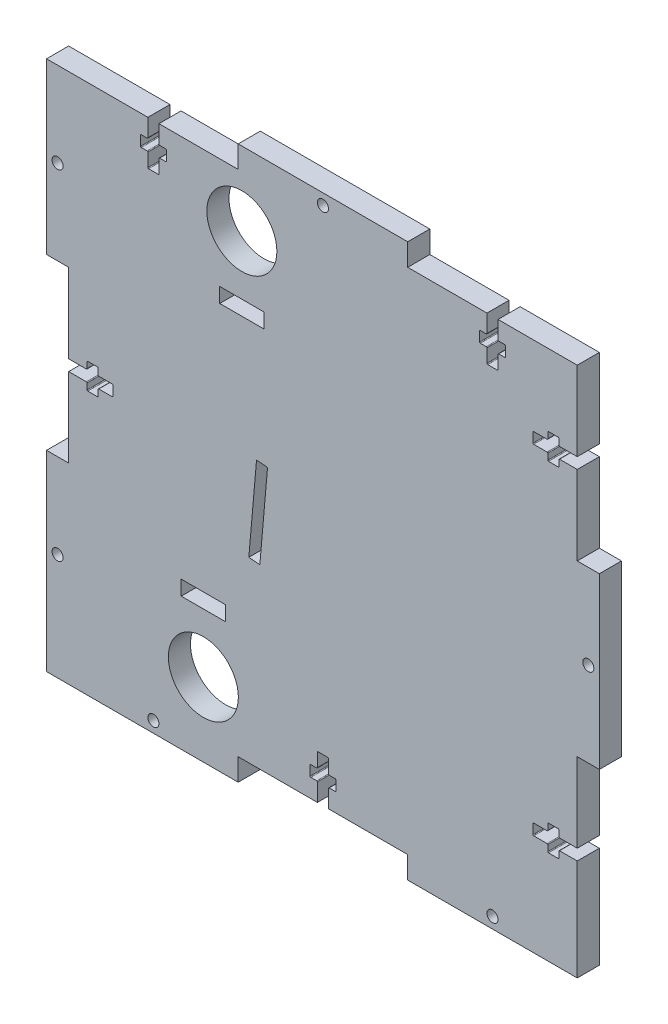
SolidWorks part; units mm, degrees
ref_plane "Front Plane" through (0, 0, 0) normal (0, 0, 1) x (1, 0, 0)
ref_plane "Top Plane" through (0, 0, 0) normal (0, 1, 0) x (1, 0, 0)
ref_plane "Right Plane" through (0, 0, 0) normal (1, 0, 0) x (0, 0, -1)
sketch "Sketch1" plane through (0, 0, 0) normal (0, 0, 1) x (1, 0, 0)
  line L0 (-69, 69) -> (-23, 69)
  line L5 (-75, -75) -> (75, -75) construction
  line L6 (-75, -75) -> (-75, 75) construction
  line L7 (-75, 75) -> (75, 75) construction
  line L8 (75, -75) -> (75, 75) construction
  line L9 (75, 23) -> (69, 23)
  line L10 (69, -23) -> (75, -23)
  line L11 (-69, -69) -> (69, -69) construction
  line L12 (-69, -69) -> (-69, 69) construction
  line L13 (-69, 69) -> (69, 69) construction
  line L14 (69, -69) -> (69, 69) construction
  line L15 (-69, -69) -> (69, 69) construction
  line L16 (69, -69) -> (69, -23)
  line L17 (-23, 69) -> (-23, 75)
  line L18 (-23, 75) -> (23, 75)
  line L19 (23, 75) -> (23, 69)
  line L20 (23, 69) -> (69, 69)
  line L21 (75, -23) -> (75, 23)
  line L22 (69, 23) -> (69, 69)
  line L23 (-75, 23) -> (-69, 23)
  line L24 (-69, 69) -> (-75, 69)
  line L25 (-75, 69) -> (-75, 23)
  line L26 (69, -69) -> (69, -75)
  line L27 (69, -75) -> (23, -75)
  line L28 (23, -75) -> (23, -69)
  line L29 (23, -69) -> (-23, -69)
  line L30 (-23, -69) -> (-23, -75)
  line L31 (-23, -75) -> (-69, -75)
  line L32 (-69, -75) -> (-69, -69) construction
  line L33 (-69, 23) -> (-69, -23)
  line L34 (-69, -23) -> (-75, -23)
  line L35 (-75, -23) -> (-75, -69)
  line L36 (-75, -69) -> (-69, -69) construction
  line L37 (-46, 69) -> (-46, -75) construction
  line L38 (-69, 69) -> (69, -69) construction
  line L39 (-75, -75) -> (-69, -75)
  line L40 (-75, -75) -> (-75, -69)
  point P0 (0, 0)
  point P6 (-7, -7)
  point P26 (0, -75)
  point P27 (-75, 0)
  dimension "D1" = 150
  dimension "D2" = 150
  dimension "D5" = 46
  dimension "D3" = 6
  dimension "D6" = 6
  dimension "D7" = 6
extrude "Box Side" add sketch "Sketch1" along normal blind 6
sketch "Sketch2" plane through (0, 0, 6) normal (0, 0, 1) x (1, 0, 0)
  line L0 (23, 72) -> (-23, 72) construction
  line L1 (23, 75) -> (23, 69) construction
  line L2 (-23, 69) -> (-23, 75) construction
  line L3 (-46, 69) -> (-46, -75) construction
  line L5 (0, 75) -> (0, 69) construction
  line L6 (-23, 75) -> (23, 75) construction
  line L7 (-69, 69) -> (69, 69) construction
  line L16 (-46, 69) -> (-46, -75) construction
  line L21 (0, -69) -> (0, 69) construction
  line L35 (-69, 69) -> (-23, 69) construction
  line L36 (-44.5, 69) -> (-44.5, 64.2)
  line L37 (-44.3, 64) -> (-42.7, 64)
  line L38 (-42.5, 63.8) -> (-42.5, 61.2)
  line L39 (-42.7, 61) -> (-44.3, 61)
  line L40 (-44.5, 60.8) -> (-44.5, 57.2)
  line L46 (-44.7, 57) -> (-47.3, 57)
  line L48 (-44.5, 69) -> (-47.5, 69)
  line L51 (-47.5, 60.8) -> (-47.5, 57.2)
  line L52 (-49.3, 61) -> (-47.7, 61)
  line L53 (-49.5, 63.8) -> (-49.5, 61.2)
  line L54 (-47.7, 64) -> (-49.3, 64)
  line L55 (-47.5, 69) -> (-47.5, 64.2)
  line L56 (47.5, 69) -> (47.5, 64.2)
  line L57 (47.7, 64) -> (49.3, 64)
  line L58 (49.5, 63.8) -> (49.5, 61.2)
  line L59 (49.3, 61) -> (47.7, 61)
  line L60 (47.5, 60.8) -> (47.5, 57.2)
  line L61 (44.5, 69) -> (47.5, 69)
  line L62 (44.7, 57) -> (47.3, 57)
  line L63 (44.5, 60.8) -> (44.5, 57.2)
  line L64 (42.7, 61) -> (44.3, 61)
  line L65 (42.5, 63.8) -> (42.5, 61.2)
  line L66 (44.3, 64) -> (42.7, 64)
  line L67 (44.5, 69) -> (44.5, 64.2)
  line L68 (-69, -69) -> (69, 69) construction
  line L69 (-69, -69) -> (69, 69) construction
  line L70 (75, 0) -> (69, 0) construction
  line L71 (72, 23) -> (72, -23) construction
  line L72 (69, 44.5) -> (64.2, 44.5)
  line L73 (64, 44.3) -> (64, 42.7)
  line L74 (63.8, 42.5) -> (61.2, 42.5)
  line L75 (61, 42.7) -> (61, 44.3)
  line L76 (60.8, 44.5) -> (57.2, 44.5)
  line L77 (57, 44.7) -> (57, 47.3)
  line L78 (69, 44.5) -> (69, 47.5)
  line L79 (60.8, 47.5) -> (57.2, 47.5)
  line L80 (61, 49.3) -> (61, 47.7)
  line L81 (63.8, 49.5) -> (61.2, 49.5)
  line L82 (64, 47.7) -> (64, 49.3)
  line L83 (69, 47.5) -> (64.2, 47.5)
  line L84 (69, -47.5) -> (64.2, -47.5)
  line L85 (64, -47.7) -> (64, -49.3)
  line L86 (63.8, -49.5) -> (61.2, -49.5)
  line L87 (61, -49.3) -> (61, -47.7)
  line L88 (60.8, -47.5) -> (57.2, -47.5)
  line L89 (69, -44.5) -> (69, -47.5)
  line L90 (57, -44.7) -> (57, -47.3)
  line L91 (60.8, -44.5) -> (57.2, -44.5)
  line L92 (61, -42.7) -> (61, -44.3)
  line L93 (63.8, -42.5) -> (61.2, -42.5)
  line L94 (64, -44.3) -> (64, -42.7)
  line L95 (69, -44.5) -> (64.2, -44.5)
  line L120 (-69, 69) -> (69, -69) construction
  line L121 (-69, 69) -> (69, -69) construction
  line L122 (-1.5, -69) -> (1.5, -69)
  line L123 (-23, -69) -> (23, -69) construction
  line L124 (1.5, -69) -> (1.5, -64.2)
  line L125 (1.7, -64) -> (3.3, -64)
  line L126 (3.5, -63.8) -> (3.5, -61.2)
  line L127 (3.3, -61) -> (1.7, -61)
  line L128 (1.5, -60.8) -> (1.5, -57.2)
  line L129 (1.3, -57) -> (-1.3, -57)
  line L130 (-1.5, -60.8) -> (-1.5, -57.2)
  line L131 (-3.3, -61) -> (-1.7, -61)
  line L132 (-3.5, -63.8) -> (-3.5, -61.2)
  line L133 (-1.7, -64) -> (-3.3, -64)
  line L134 (-1.5, -69) -> (-1.5, -64.2)
  line L135 (-69, -1.5) -> (-64.2, -1.5)
  line L136 (-64, -1.7) -> (-64, -3.3)
  line L137 (-63.8, -3.5) -> (-61.2, -3.5)
  line L138 (-61, -3.3) -> (-61, -1.7)
  line L139 (-60.8, -1.5) -> (-57.2, -1.5)
  line L140 (-57, 1.3) -> (-57, -1.3)
  line L141 (-60.8, 1.5) -> (-57.2, 1.5)
  line L142 (-61, 3.3) -> (-61, 1.7)
  line L143 (-63.8, 3.5) -> (-61.2, 3.5)
  line L144 (-64, 1.7) -> (-64, 3.3)
  line L145 (-69, 1.5) -> (-64.2, 1.5)
  line L146 (-69, -1.5) -> (-69, 1.5)
  line L147 (-69, -72) -> (-23, -72) construction
  line L148 (-23, 69) -> (-75, 69) construction
  line L149 (-23, -75) -> (-23, -69) construction
  line L150 (-69, -69) -> (-69, -75) construction
  line L151 (-75, -75) -> (-23, -75) construction
  circle A0 centre (0, 72) radius 1.5
  arc A1 (-44.5, 57.2) -> (-44.7, 57) centre (-44.7, 57.2) cw
  arc A2 (-44.3, 61) -> (-44.5, 60.8) centre (-44.3, 60.8) ccw
  arc A3 (-42.5, 61.2) -> (-42.7, 61) centre (-42.7, 61.2) cw
  arc A4 (-42.7, 64) -> (-42.5, 63.8) centre (-42.7, 63.8) cw
  arc A5 (-44.5, 64.2) -> (-44.3, 64) centre (-44.3, 64.2) ccw
  arc A6 (-47.5, 64.2) -> (-47.7, 64) centre (-47.7, 64.2) cw
  arc A7 (-49.3, 64) -> (-49.5, 63.8) centre (-49.3, 63.8) ccw
  arc A8 (-49.5, 61.2) -> (-49.3, 61) centre (-49.3, 61.2) ccw
  arc A9 (-47.7, 61) -> (-47.5, 60.8) centre (-47.7, 60.8) cw
  arc A10 (-47.5, 57.2) -> (-47.3, 57) centre (-47.3, 57.2) ccw
  arc A11 (47.5, 57.2) -> (47.3, 57) centre (47.3, 57.2) cw
  arc A12 (47.7, 61) -> (47.5, 60.8) centre (47.7, 60.8) ccw
  arc A13 (49.5, 61.2) -> (49.3, 61) centre (49.3, 61.2) cw
  arc A14 (49.3, 64) -> (49.5, 63.8) centre (49.3, 63.8) cw
  arc A15 (47.5, 64.2) -> (47.7, 64) centre (47.7, 64.2) ccw
  arc A16 (44.5, 64.2) -> (44.3, 64) centre (44.3, 64.2) cw
  arc A17 (42.7, 64) -> (42.5, 63.8) centre (42.7, 63.8) ccw
  arc A18 (42.5, 61.2) -> (42.7, 61) centre (42.7, 61.2) ccw
  arc A19 (44.3, 61) -> (44.5, 60.8) centre (44.3, 60.8) cw
  arc A20 (44.5, 57.2) -> (44.7, 57) centre (44.7, 57.2) ccw
  arc A21 (57.2, 44.5) -> (57, 44.7) centre (57.2, 44.7) cw
  arc A22 (61, 44.3) -> (60.8, 44.5) centre (60.8, 44.3) ccw
  arc A23 (61.2, 42.5) -> (61, 42.7) centre (61.2, 42.7) cw
  arc A24 (64, 42.7) -> (63.8, 42.5) centre (63.8, 42.7) cw
  arc A25 (64.2, 44.5) -> (64, 44.3) centre (64.2, 44.3) ccw
  arc A26 (64.2, 47.5) -> (64, 47.7) centre (64.2, 47.7) cw
  arc A27 (64, 49.3) -> (63.8, 49.5) centre (63.8, 49.3) ccw
  arc A28 (61.2, 49.5) -> (61, 49.3) centre (61.2, 49.3) ccw
  arc A29 (61, 47.7) -> (60.8, 47.5) centre (60.8, 47.7) cw
  arc A30 (57.2, 47.5) -> (57, 47.3) centre (57.2, 47.3) ccw
  arc A31 (57.2, -47.5) -> (57, -47.3) centre (57.2, -47.3) cw
  arc A32 (61, -47.7) -> (60.8, -47.5) centre (60.8, -47.7) ccw
  arc A33 (61.2, -49.5) -> (61, -49.3) centre (61.2, -49.3) cw
  arc A34 (64, -49.3) -> (63.8, -49.5) centre (63.8, -49.3) cw
  arc A35 (64.2, -47.5) -> (64, -47.7) centre (64.2, -47.7) ccw
  arc A36 (64.2, -44.5) -> (64, -44.3) centre (64.2, -44.3) cw
  arc A37 (64, -42.7) -> (63.8, -42.5) centre (63.8, -42.7) ccw
  arc A38 (61.2, -42.5) -> (61, -42.7) centre (61.2, -42.7) ccw
  arc A39 (61, -44.3) -> (60.8, -44.5) centre (60.8, -44.3) cw
  arc A40 (57.2, -44.5) -> (57, -44.7) centre (57.2, -44.7) ccw
  circle A41 centre (72, 0) radius 1.5
  arc A62 (1.5, -57.2) -> (1.3, -57) centre (1.3, -57.2) ccw
  arc A63 (1.7, -61) -> (1.5, -60.8) centre (1.7, -60.8) cw
  arc A64 (3.5, -61.2) -> (3.3, -61) centre (3.3, -61.2) ccw
  arc A65 (3.3, -64) -> (3.5, -63.8) centre (3.3, -63.8) ccw
  arc A66 (1.5, -64.2) -> (1.7, -64) centre (1.7, -64.2) cw
  arc A67 (-1.5, -64.2) -> (-1.7, -64) centre (-1.7, -64.2) ccw
  arc A68 (-3.3, -64) -> (-3.5, -63.8) centre (-3.3, -63.8) cw
  arc A69 (-3.5, -61.2) -> (-3.3, -61) centre (-3.3, -61.2) cw
  arc A70 (-1.7, -61) -> (-1.5, -60.8) centre (-1.7, -60.8) ccw
  arc A71 (-1.5, -57.2) -> (-1.3, -57) centre (-1.3, -57.2) cw
  arc A72 (-57.2, -1.5) -> (-57, -1.3) centre (-57.2, -1.3) ccw
  arc A73 (-61, -1.7) -> (-60.8, -1.5) centre (-60.8, -1.7) cw
  arc A74 (-61.2, -3.5) -> (-61, -3.3) centre (-61.2, -3.3) ccw
  arc A75 (-64, -3.3) -> (-63.8, -3.5) centre (-63.8, -3.3) ccw
  arc A76 (-64.2, -1.5) -> (-64, -1.7) centre (-64.2, -1.7) cw
  arc A77 (-64.2, 1.5) -> (-64, 1.7) centre (-64.2, 1.7) ccw
  arc A78 (-64, 3.3) -> (-63.8, 3.5) centre (-63.8, 3.3) cw
  arc A79 (-61.2, 3.5) -> (-61, 3.3) centre (-61.2, 3.3) cw
  arc A80 (-61, 1.7) -> (-60.8, 1.5) centre (-60.8, 1.7) ccw
  arc A81 (-57.2, 1.5) -> (-57, 1.3) centre (-57.2, 1.3) cw
  circle A82 centre (-46, -72) radius 1.5
  circle A83 centre (46, -72) radius 1.5
  circle A84 centre (-72, 46) radius 1.5
  circle A85 centre (-72, -46) radius 1.5
  point P6 (0, 72)
  point P38 (0, 0)
  point P56 (-46, 57)
  point P88 (46, 57)
  point P161 (57, 46)
  point P162 (57, -46)
  point P198 (0, -57)
  point P231 (-57, 0)
  point P234 (-42.5, 62.5)
  dimension "D1" = 3
  dimension "D2" = 0.2
  dimension "D8" = 0.2
  dimension "D14" = 3
  dimension "D4" = 3
  dimension "D7" = 1.5
  dimension "D10" = 3
  dimension "D12" = 1.5
  dimension "D9" = 12
  dimension "D11" = 5
  dimension "D13" = 7
  dimension "D3" = 12
  dimension "D5" = 7
  dimension "D6" = 5
extrude "Screw Cut-outs" cut sketch "Sketch2" against normal through all
sketch "Sketch3" plane through (0, 0, 6) normal (0, 0, 1) x (1, 0, 0)
  line L0 (-23, 69) -> (-44.5, 69) construction
  line L1 (-69, 23) -> (-69, 1.5) construction
  circle A0 centre (-22, 55) radius 9.5
  circle A1 centre (-32.45, -55) radius 9.5
  circle A2 centre (-32.45, -55) radius 6.5 construction
  dimension "D1" = 19
  dimension "D4" = 19
  dimension "D7" = 13
  dimension "D2" = 14
  dimension "D3" = 47
  dimension "D5" = 10.45
  dimension "D6" = 110
extrude "Cut-Extrude1" cut sketch "Sketch3" against normal through all
sketch "Sketch4" plane through (0, 0, 6) normal (0, 0, 1) x (1, 0, 0)
  line L0 (-24.9996, 51) -> (49975.0004, 51) construction
  line L1 (-23, 69) -> (-44.5, 69) construction
  line L2 (-13.84, 51) -> (-13.84, 69) construction
  line L3 (69, 47.5) -> (69, 69) construction
  line L4 (-13.84, 51) -> (-25.7981, -85.6815) construction
  line L5 (-13.84, 51) -> (49795.8949, -4306.7871) construction
  line L6 (-10.8514, 50.7385) -> (-4368.6386, -49758.9964) construction
  line L7 (-20.1126, -20.6961) -> (-17.124, -20.9576)
  line L8 (-17.124, -20.9576) -> (-15.0323, 2.9511)
  line L9 (-15.0323, 2.9511) -> (-18.0209, 3.2125)
  line L10 (-18.0209, 3.2125) -> (-20.1126, -20.6961)
  dimension "D1" = 18
  dimension "D2" = 82.84
  dimension "D3" = 5
  dimension "D4" = 3
  dimension "D5" = 24
  dimension "D6" = 47.97
extrude "Cut-Extrude2" cut sketch "Sketch4" against normal through all
sketch "Sketch5" plane through (0, 0, 6) normal (0, 0, 1) x (1, 0, 0)
  line L1 (-38.45, -39) -> (-26.45, -39)
  line L2 (-38.45, -39) -> (-38.45, -35)
  line L3 (-38.45, -35) -> (-26.45, -35)
  line L4 (-26.45, -39) -> (-26.45, -35)
  line L5 (-28, 35) -> (-16, 35)
  line L6 (-28, 35) -> (-28, 39)
  line L7 (-28, 39) -> (-16, 39)
  line L8 (-16, 35) -> (-16, 39)
  point P8 (-32.45, -55)
  point P9 (-22, 55)
  point P11 (-22, 39)
  point P13 (-32.45, -39)
  point P14 (0, 0)
  point P15 (0, 0)
  dimension "D1" = 16
  dimension "D2" = 16
  dimension "D3" = 4
  dimension "D4" = 12
extrude "Cut-Extrude3" cut sketch "Sketch5" against normal through all
equation "\"filletRadius\"=0.2"
equation "\"D8@Sketch2\"=\"filletRadius\""
equation "\"D2@Sketch2\"=\"filletRadius\""
equation "\"fingerWidth\"= 46"
equation "\"D5@Sketch1\"=\"fingerWidth\""
equation "\"wallThickness\"= 6"
equation "\"D3@Sketch1\" = \"wallThickness\""
equation "\"D6@Sketch1\" = \"wallThickness\""
equation "\"D7@Sketch1\" = \"wallThickness\""
equation "\"D1@Box Side\" = \"wallThickness\""
equation "\"M3\"= 3"
equation "\"D14@Sketch2\"=\"M3\""
equation "\"D1@Sketch2\"=\"M3\""
equation "\"D12@Sketch2\"=\"M3\"/2"
equation "\"nutThickness\"=3"
equation "\"D10@Sketch2\" = \"nutThickness\""
equation "\"boltLength\"= 12"
equation "\"D9@Sketch2\" = \"boltLength\""
equation "\"distanceToNut\"= 5"
equation "\"D11@Sketch2\" = \"distanceToNut\""
equation "\"D13@Sketch2\" = \"nutWidth\""
equation "\"D7@Sketch2\"=\"M3\"/2"
equation "\"D4@Sketch2\" = \"nutThickness\""
equation "\"D3@Sketch2\" = \"boltLength\""
equation "\"D5@Sketch2\" = \"nutWidth\""
equation "\"D6@Sketch2\" = \"distanceToNut\""
equation "\"sideLength\"=150"
equation "\"D1@Sketch1\"=\"sideLength\""
equation "\"D2@Sketch1\"=\"sideLength\""
equation "\"nutWidth\"=7"
